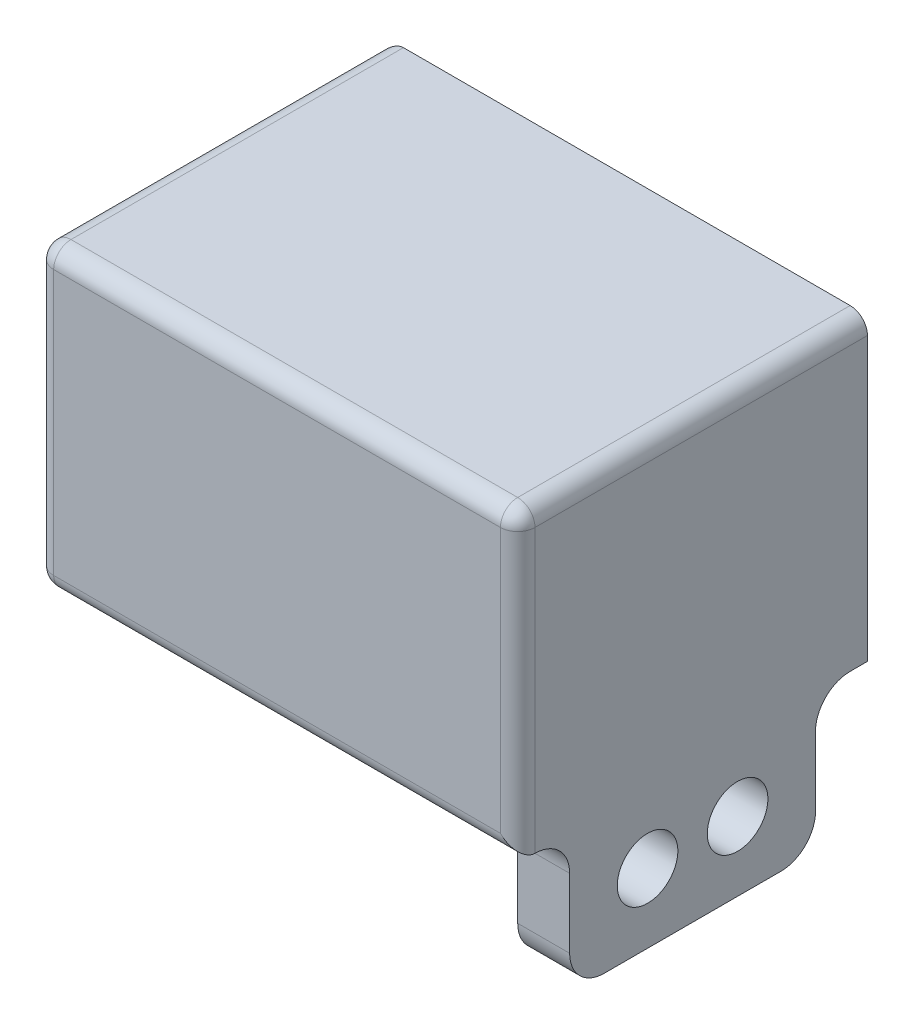
SolidWorks part; units mm, degrees
ref_plane "Front Plane" through (0, 0, 0) normal (0, 0, 1) x (1, 0, 0)
ref_plane "Top Plane" through (0, 0, 0) normal (0, 1, 0) x (1, 0, 0)
ref_plane "Right Plane" through (0, 0, 0) normal (1, 0, 0) x (0, 0, -1)
sketch "Sketch1" plane through (0, 0, 0) normal (0, 0, 1) x (1, 0, 0)
  line L1 (11.4, -6.15) -> (-11.4, -6.15)
  line L2 (11.4, -6.15) -> (11.4, 6.15)
  line L3 (11.4, 6.15) -> (-11.4, 6.15)
  line L4 (-11.4, -6.15) -> (-11.4, 6.15)
  line L5 (11.4, -6.15) -> (-11.4, 6.15) construction
  line L6 (11.4, 6.15) -> (-11.4, -6.15) construction
  point P0 (0, 0)
  dimension "D1" = 22.8
  dimension "D2" = 12.3
extrude "Boss-Extrude1" add sketch "Sketch1" along normal blind 2
sketch "Sketch2" plane through (0, 0, 2) normal (0, 0, 1) x (1, 0, 0)
  line L1 (11.4, -6.15) -> (-11.4, -6.15)
  line L2 (11.4, -6.15) -> (11.4, 6.15)
  line L3 (11.4, 6.15) -> (-11.4, 6.15)
  line L4 (-11.4, -6.15) -> (-11.4, 6.15)
  line L5 (11.4, -6.15) -> (-11.4, 6.15) construction
  line L6 (11.4, 6.15) -> (-11.4, -6.15) construction
  line L7 (16.4, -8.65) -> (-16.4, -8.65)
  line L8 (16.4, -8.65) -> (16.4, 8.65)
  line L9 (16.4, 8.65) -> (-16.4, 8.65)
  line L10 (-16.4, -8.65) -> (-16.4, 8.65)
  line L11 (16.4, -8.65) -> (-16.4, 8.65) construction
  line L12 (16.4, 8.65) -> (-16.4, -8.65) construction
  point P0 (0, 0)
  point P7 (0, 0)
  dimension "D1" = 2.5
  dimension "D2" = 5
extrude "Boss-Extrude2" add sketch "Sketch2" against normal blind 20.2
sketch "Sketch3" plane through (-16.4, 0, 0) normal (-1, 0, 0) x (0, 0, 1)
  line L0 (2, 8.65) -> (2, -8.65) construction
  line L1 (-18.2, -5.65) -> (-3, -5.65)
  line L2 (-18.2, -5.65) -> (-18.2, 5.65)
  line L3 (-18.2, 5.65) -> (-3, 5.65)
  line L4 (-3, -5.65) -> (-3, 5.65)
  line L5 (-18.2, -5.65) -> (-3, 5.65) construction
  line L6 (-18.2, 5.65) -> (-3, -5.65) construction
  line L7 (-18.2, 8.65) -> (-18.2, -8.65) construction
  line L8 (-18.2, 8.65) -> (2, 8.65) construction
  line L9 (-18.2, -8.65) -> (2, -8.65) construction
  point P0 (-10.6, 0)
  dimension "D1" = 5
  dimension "D2" = 0
  dimension "D3" = 3
  dimension "D4" = 3
extrude "Cut-Extrude1" cut sketch "Sketch3" against normal up to surface (5 mm away) up to face at (-11.4, 0, -9.1)
fillet "Fillet1" radius 1 2 edges at (-13.9, -5.65, -3) (-13.9, 5.65, -3)
sketch "Sketch4" plane through (0, 0, -18.2) normal (0, 0, -1) x (-1, 0, 0)
  line L0 (-16.4, 0) -> (-13, 0) construction
  line L1 (-16.4, -8.65) -> (-16.4, 8.65) construction
  circle A0 centre (-13.75, 0) radius 0.75
  dimension "D1" = 1.5
  dimension "D3" = 2.65
extrude "Cut-Extrude2" cut sketch "Sketch4" against normal blind 5
sketch "Sketch5" plane through (0, 0, -18.2) normal (0, 0, -1) x (-1, 0, 0)
  line L0 (16.4, -8.65) -> (-16.4, -8.65) construction
  line L1 (16.4, 8.65) -> (12.9, 8.65)
  line L2 (16.4, 8.65) -> (16.4, -8.65)
  line L3 (16.4, -8.65) -> (12.9, -8.65)
  line L4 (12.9, 8.65) -> (12.9, -8.65)
  dimension "D1" = 3.5
extrude "Cut-Extrude3" cut sketch "Sketch5" against normal through all
fillet "Fillet2" radius 1 11 edges at (16.4, 8.65, -8.1) (-12.9, -8.65, -8.1) (-12.9, 8.65, -8.1) (-12.9, -5.65, -11.1) (-12.9, -5.3571, -3.2929) (-12.9, 0, -3) (-12.9, 5.3571, -3.2929) (-12.9, 5.65, -11.1) (-12.9, 7.15, -18.2) (-12.9, 0, 2) (-12.9, -7.15, -18.2)
sketch "Sketch8" plane through (16.4, 0, 0) normal (1, 0, 0) x (0, 0, -1)
  line L1 (1, -8.65) -> (15.2, -8.65)
  line L2 (1, -8.65) -> (1, -16.65)
  line L3 (1, -16.65) -> (15.2, -16.65)
  line L4 (15.2, -8.65) -> (15.2, -16.65)
  line L5 (-2, -8.65) -> (-2, 7.65) construction
  line L6 (18.2, -8.65) -> (18.2, 7.65) construction
  line L8 (18.2, -8.65) -> (-2, -8.65) construction
  dimension "D1" = 3
  dimension "D2" = 8
  dimension "D3" = 3
extrude "Boss-Extrude4" add sketch "Sketch8" against normal blind 3
sketch "Sketch9" plane through (13.4, 0, 0) normal (-1, 0, 0) x (0, 0, 1)
  line L0 (-15.2, -12.65) -> (-1, -12.65) construction
  line L1 (-15.2, -16.65) -> (-15.2, -8.65) construction
  line L2 (-1, -8.65) -> (-1, -16.65) construction
  circle A0 centre (-10.7, -12.65) radius 1.75
  circle A1 centre (-5.5, -12.65) radius 1.75
  dimension "D1" = 3.5
  dimension "D2" = 3.5
  dimension "D3" = 4.5
  dimension "D4" = 4.5
extrude "Cut-Extrude5" cut sketch "Sketch9" against normal through all
fillet "Fillet4" radius 2 4 edges at (14.9, -8.65, -1) (14.9, -16.65, -1) (14.9, -16.65, -15.2) (14.9, -8.65, -15.2)
sketch "Sketch10" plane through (0, 0, -18.2) normal (0, 0, -1) x (-1, 0, 0)
  line L0 (11.4, -6.15) -> (11.4, 9.8681) construction
  line L1 (11.4, 9.8681) -> (11.4, -11.2456) construction
  line L2 (-15.4, 8.65) -> (11.9, 8.65) construction
  line L3 (11.4, 8.65) -> (13.6958, 8.65)
  line L4 (11.4, 8.65) -> (11.4, -8.65)
  line L5 (11.4, -8.65) -> (13.6958, -8.65)
  line L6 (13.6958, 8.65) -> (13.6958, -8.65)
  line L7 (10.9641, -8.65) -> (17.1064, -8.65) construction
  line L8 (11.9, -8.65) -> (-16.4, -8.65) construction
  dimension "D1" = 2.2958
extrude "Cut-Extrude6" cut sketch "Sketch10" against normal through all
fillet "Fillet5" radius 1 12 edges at (16.4, -0.5, 2) (16.1071, 8.3571, 2) (-11.4, 6.15, -9.1) (-11.4, 7.4, -18.2) (-11.4, 8.65, -8.1) (-11.4, 0, 2) (-11.4, -8.65, -8.1) (-11.4, -7.4, -18.2) (-11.4, -6.15, -9.1) (-11.4, 0, 0) (2.5, -8.65, 2) (2, 8.65, 2)
fillet "Fillet6" radius 1 1 edges at (13.4, -8.65, -8.1)
